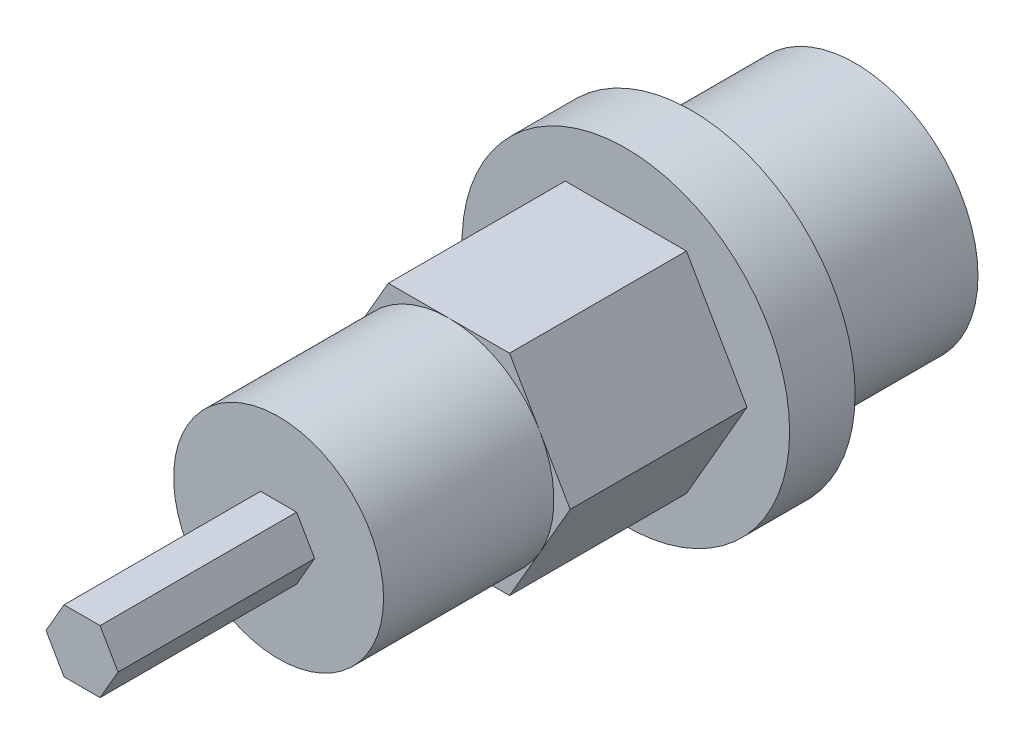
SolidWorks part; units mm, degrees
ref_plane "Front Plane" through (0, 0, 0) normal (0, 0, 1) x (1, 0, 0)
ref_plane "Top Plane" through (0, 0, 0) normal (0, 1, 0) x (1, 0, 0)
ref_plane "Right Plane" through (0, 0, 0) normal (1, 0, 0) x (0, 0, -1)
sketch "Sketch1" plane through (0, 0, 0) normal (0, 0, 1) x (1, 0, 0)
  circle A0 centre (0, 0) radius 3.75
  dimension "D1" = 7.5
extrude "Boss-Extrude1" add sketch "Sketch1" along normal blind 5
sketch "Sketch2" plane through (0, 0, 5) normal (0, 0, 1) x (1, 0, 0)
  circle A0 centre (0, 0) radius 5
  dimension "D1" = 10
extrude "Boss-Extrude2" add sketch "Sketch2" along normal blind 2
sketch "Sketch3" plane through (0, 0, 7) normal (0, 0, 1) x (1, 0, 0)
  line L7 (3.7, 0) -> (1.85, 3.2043)
  line L8 (1.85, 3.2043) -> (-1.85, 3.2043)
  line L9 (-1.85, 3.2043) -> (-3.7, 0)
  line L10 (-3.7, 0) -> (-1.85, -3.2043)
  line L11 (-1.85, -3.2043) -> (1.85, -3.2043)
  line L12 (1.85, -3.2043) -> (3.7, 0)
  circle A0 centre (0, 0) radius 3.7 construction
  circle A1 centre (0, 0) radius 3.2043 construction
  dimension "D1" = 7.4
extrude "Boss-Extrude3" add sketch "Sketch3" along normal blind 5.4
sketch "Sketch4" plane through (0, 0, 12.4) normal (0, 0, 1) x (1, 0, 0)
  line L2 (-1.85, 3.2043) -> (-3.7, 0) construction
  circle A0 centre (0, 0) radius 3.2043
extrude "Boss-Extrude4" add sketch "Sketch4" along normal blind 5.2
sketch "Sketch5" plane through (0, 0, 17.6) normal (0, 0, 1) x (1, 0, 0)
  line L1 (1.1, 0) -> (0.55, 0.9526)
  line L2 (0.55, 0.9526) -> (-0.55, 0.9526)
  line L3 (-0.55, 0.9526) -> (-1.1, 0)
  line L4 (-1.1, 0) -> (-0.55, -0.9526)
  line L5 (-0.55, -0.9526) -> (0.55, -0.9526)
  line L6 (0.55, -0.9526) -> (1.1, 0)
  circle A0 centre (0, 0) radius 0.9526 construction
  point P1 (0, 0)
  dimension "D1" = 1.1
extrude "Boss-Extrude5" add sketch "Sketch5" along normal blind 6
